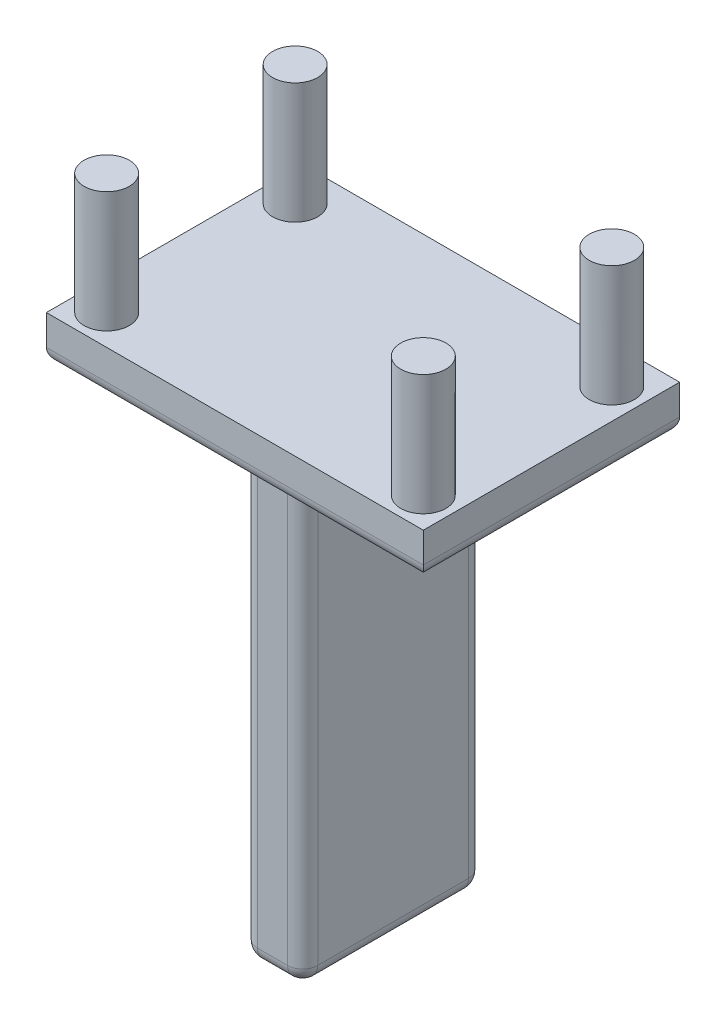
SolidWorks part; units mm, degrees
ref_plane "Front Plane" through (0, 0, 0) normal (0, 0, 1) x (1, 0, 0)
ref_plane "Top Plane" through (0, 0, 0) normal (0, 1, 0) x (1, 0, 0)
ref_plane "Right Plane" through (0, 0, 0) normal (1, 0, 0) x (0, 0, -1)
sketch "Sketch1" plane through (0, 0, 0) normal (0, 1, 0) x (1, 0, 0)
  line L1 (-12.5, -8.5) -> (12.5, -8.5)
  line L2 (-12.5, -8.5) -> (-12.5, 8.5)
  line L3 (-12.5, 8.5) -> (12.5, 8.5)
  line L4 (12.5, -8.5) -> (12.5, 8.5)
  line L5 (-12.5, -8.5) -> (12.5, 8.5) construction
  line L6 (-12.5, 8.5) -> (12.5, -8.5) construction
  point P0 (0, 0)
  dimension "D1" = 25
  dimension "D2" = 17
extrude "Boss-Extrude1" add sketch "Sketch1" along normal blind 3
sketch "Sketch2" plane through (0, 3, 0) normal (0, 1, 0) x (1, 0, 0)
  circle A0 centre (-10.5, -6.5) radius 1.5
  circle A1 centre (10.5, -6.5) radius 1.5
  circle A2 centre (10.5, 6) radius 1.5
  circle A3 centre (-10.5, 6) radius 1.5
extrude "Boss-Extrude2" add sketch "Sketch2" along normal blind 8
sketch "Sketch3" plane through (0, 0, 0) normal (0, -1, 0) x (1, 0, 0)
  line L1 (-2, -6) -> (2, -6)
  line L2 (-2, -6) -> (-2, 6)
  line L3 (-2, 6) -> (2, 6)
  line L4 (2, -6) -> (2, 6)
  line L5 (-2, -6) -> (2, 6) construction
  line L6 (-2, 6) -> (2, -6) construction
  point P0 (0, 0)
  dimension "D1" = 4
  dimension "D2" = 12
extrude "Boss-Extrude3" add sketch "Sketch3" along normal blind 30
fillet "Fillet1" radius 1 4 edges at (2, -15, -6) (-2, -15, -6) (-2, -15, 6) (2, -15, 6)
fillet "Fillet2" radius 1 8 edges at (-1.7071, -30, -5.7071) (-2, -30, 0) (-1.7071, -30, 5.7071) (0, -30, 6) (1.7071, -30, 5.7071) (2, -30, 0) (1.7071, -30, -5.7071) (0, -30, -6)
fillet "Fillet3" radius 1 12 edges at (0, 0, -8.5) (-12.5, 0, 0) (0, 0, 8.5) (12.5, 0, 0) (1.7071, 0, 5.7071) (0, 0, 6) (-1.7071, 0, 5.7071) (-2, 0, 0) (-1.7071, 0, -5.7071) (0, 0, -6) (1.7071, 0, -5.7071) (2, 0, 0)
